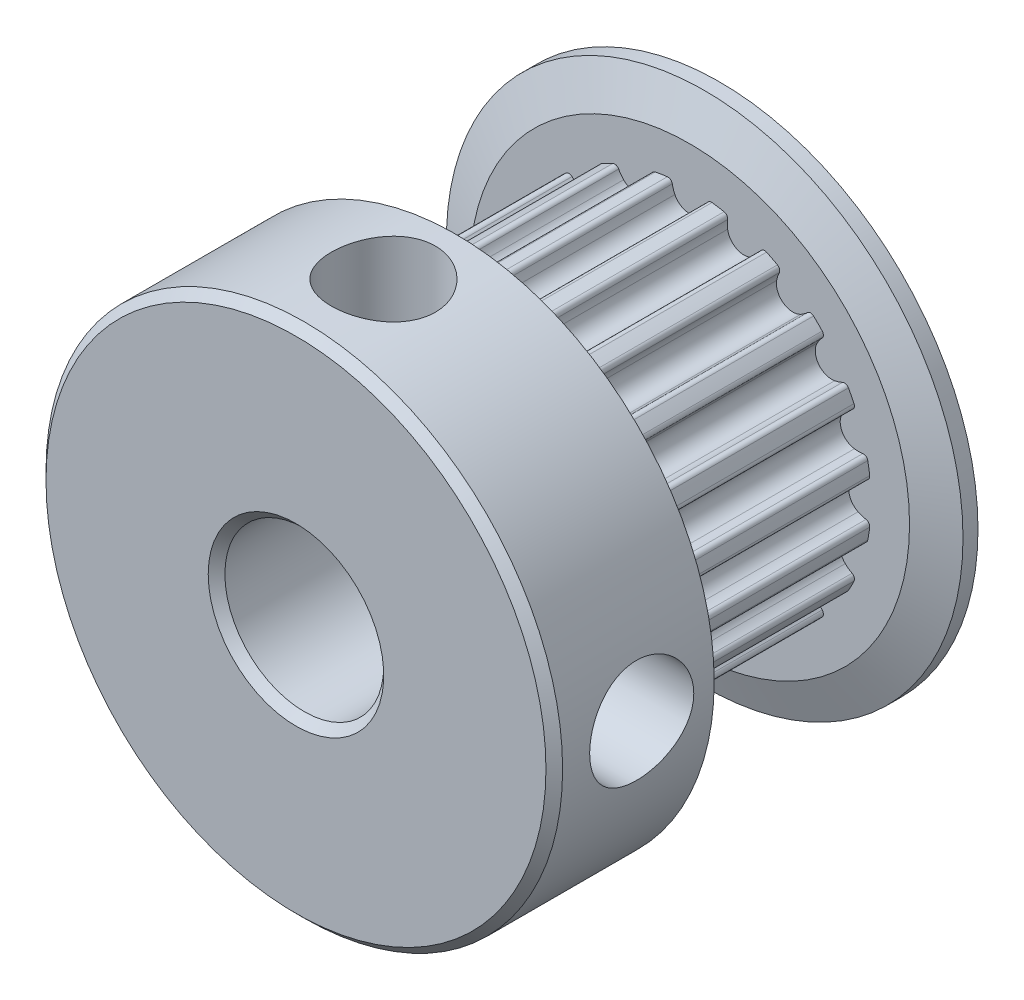
SolidWorks part; units mm, degrees
ref_plane "Front Plane" through (0, 0, 0) normal (0, 0, 1) x (1, 0, 0)
ref_plane "Top Plane" through (0, 0, 0) normal (0, 1, 0) x (1, 0, 0)
ref_plane "Right Plane" through (0, 0, 0) normal (1, 0, 0) x (0, 0, -1)
sketch "Sketch1" plane through (0, 0, 0) normal (0, 0, 1) x (1, 0, 0)
  line L1 (-1.7499, 5.3585) -> (1.7499, 5.3585) construction
  line L4 (0, 0) -> (0, 5.3585) construction
  line L5 (0, 5.3585) -> (0, 11.2119) construction
  line L6 (0, 6.3625) -> (1.9751, 6.0482) construction
  line L7 (1.9751, 6.0482) -> (2.6648, 5.8229) construction
  line L8 (1.9751, 6.0482) -> (1.7499, 5.3585) construction
  line L9 (-1.9751, 6.0482) -> (-1.7499, 5.3585) construction
  line L10 (-1.8963, 5.8067) -> (-2.841, 8.6995)
  line L11 (-2.841, 8.6995) -> (2.841, 8.6995)
  line L12 (2.841, 8.6995) -> (1.8963, 5.8067)
  circle A0 centre (0, 0) radius 6.3625 construction
  circle A1 centre (0, 0) radius 8.6995 construction
  circle A2 centre (0, 0) radius 6.1085 construction
  arc A3 (-0.4989, 5.6703) -> (0.4989, 5.6703) centre (0, 5.9135) ccw
  arc A4 (-0.4989, 5.6703) -> (-0.5855, 5.9387) centre (0.4, 6.1085) cw
  arc A5 (-1.8963, 5.8067) -> (-0.7518, 6.0621) centre (0, 0) cw
  arc A6 (-0.5855, 5.9387) -> (-0.7518, 6.0621) centre (-0.7333, 5.9132) ccw
  arc A7 (1.8963, 5.8067) -> (0.7518, 6.0621) centre (0, 0) ccw
  arc A8 (0.5855, 5.9387) -> (0.7518, 6.0621) centre (0.7333, 5.9132) cw
  arc A9 (0.4989, 5.6703) -> (0.5855, 5.9387) centre (-0.4, 6.1085) ccw
  point P6 (0, 20.9083)
  point P11 (0, 6.3625)
  point P13 (0, 8.6995)
  point P14 (0, 6.1085)
  dimension "D1" = 9.6964
  dimension "D2" = 4.8494
sketch "Sketch2" plane through (0, 0, 0) normal (1, 0, 0) x (0, 0, -1)
  line L0 (-7.135, 2.675) -> (7.135, 2.675)
  line L1 (-7.135, 2.675) -> (-7.135, 8.6995)
  line L2 (-1.75, 8.6995) -> (-7.135, 8.6995)
  line L3 (-2.255, 2.675) -> (-2.255, 8.6995) construction
  line L4 (-2.255, 8.6995) -> (-1.245, 8.6995) construction
  line L5 (-1.245, 8.6995) -> (-1.245, 6.1085) construction
  line L6 (-1.245, 6.1085) -> (6.125, 6.1085)
  line L7 (6.125, 6.1085) -> (6.125, 8.6995) construction
  line L8 (6.125, 8.6995) -> (7.135, 8.6995) construction
  line L9 (7.135, 8.6995) -> (7.135, 2.675)
  line L10 (-7.135, 0) -> (7.135, 0) construction
  line L11 (6.63, 8.6995) -> (6.125, 7.404)
  line L12 (-1.245, 7.404) -> (-1.75, 8.6995)
  line L14 (-1.245, 7.404) -> (-1.245, 6.1085)
  line L15 (6.125, 6.1085) -> (6.125, 7.404)
  line L16 (6.63, 8.6995) -> (7.135, 8.6995)
  arc A0 (-1.245, 7.404) -> (-1.75, 8.6995) centre (-3.1592, 7.404) ccw construction
  arc A1 (6.125, 7.404) -> (6.63, 8.6995) centre (8.0392, 7.404) cw construction
  point P12 (-1.245, 7.404)
  point P14 (-1.75, 8.6995)
  point P20 (6.125, 7.404)
  point P21 (6.63, 8.6995)
  point P25 (6.125, 0)
  point P26 (-1.245, 0)
  dimension "OA" = 14.27
  dimension "Bore" = 5.35
  dimension "Outside Width" = 8.38
  dimension "Inside Width" = 7.37
revolve "Revolve1" add sketch "Sketch2" angle 360 mid plane about L10
sketch "Sketch3" plane through (0, 0, 0) normal (0, 0, 1) x (1, 0, 0)
  line L6 (2.841, 8.6995) -> (-2.841, 8.6995)
  line L7 (1.8963, 5.8067) -> (2.841, 8.6995)
  line L8 (-2.841, 8.6995) -> (-1.8963, 5.8067)
  line L9 (2.841, 8.6995) -> (-2.841, 8.6995)
  line L10 (1.8963, 5.8067) -> (2.841, 8.6995)
  line L11 (-2.841, 8.6995) -> (-1.8963, 5.8067)
  arc A8 (1.8963, 5.8067) -> (0.7518, 6.0621) centre (0, 0) ccw
  arc A9 (0.7518, 6.0621) -> (0.5855, 5.9387) centre (0.7333, 5.9132) ccw
  arc A10 (0.4989, 5.6703) -> (0.5855, 5.9387) centre (-0.4, 6.1085) ccw
  arc A11 (-0.4989, 5.6703) -> (0.4989, 5.6703) centre (0, 5.9135) ccw
  arc A12 (-0.5855, 5.9387) -> (-0.4989, 5.6703) centre (0.4, 6.1085) ccw
  arc A13 (-0.5855, 5.9387) -> (-0.7518, 6.0621) centre (-0.7333, 5.9132) ccw
  arc A14 (-0.7518, 6.0621) -> (-1.8963, 5.8067) centre (0, 0) ccw
  arc A15 (1.8963, 5.8067) -> (0.7518, 6.0621) centre (0, 0) ccw
  arc A16 (0.7518, 6.0621) -> (0.5855, 5.9387) centre (0.7333, 5.9132) ccw
  arc A17 (0.4989, 5.6703) -> (0.5855, 5.9387) centre (-0.4, 6.1085) ccw
  arc A18 (-0.4989, 5.6703) -> (0.4989, 5.6703) centre (0, 5.9135) ccw
  arc A19 (-0.5855, 5.9387) -> (-0.4989, 5.6703) centre (0.4, 6.1085) ccw
  arc A20 (-0.5855, 5.9387) -> (-0.7518, 6.0621) centre (-0.7333, 5.9132) ccw
  arc A21 (-0.7518, 6.0621) -> (-1.8963, 5.8067) centre (0, 0) ccw
  dimension "D1" = 0
extrude "Cut-Extrude1" cut sketch "Sketch3" against normal up to vertex (6.125 mm away) from vertex up to point (0, 6.1085, -6.125) starting at point (0, 6.1085, 1.245)
pattern_circular "CirPattern1" count 20 over 360 about axis through (0, 0, 7.135) along (0, 0, 1) of "Cut-Extrude1"
sketch "Sketch4" plane through (0, 0, 0) normal (1, 0, 0) x (0, -1, 0)
  line L0 (0, -1.245) -> (0, -7.135) construction
  line L1 (-2.675, -7.135) -> (2.675, -7.135) construction
  line L2 (7.404, -1.245) -> (-7.404, -1.245) construction
  circle A0 centre (0, -4.19) radius 1.7526
extrude "Cut-Extrude2" cut sketch "Sketch4" along normal through all
ref_plane "Plane1" through (0, 0, 4.19) normal (0, 0, 1) x (1, 0, 0)
sketch "Sketch5" plane through (0, 0, 4.19) normal (0, 0, 1) x (1, 0, 0)
  line L0 (0, 0) -> (0, 8.6995) construction
  line L1 (2.675, -1.3716) -> (2.675, 0)
  line L2 (3.056, -1.7526) -> (8.1401, -1.7526)
  line L3 (2.675, 0) -> (8.6995, 0) construction
  line L4 (2.675, 0) -> (8.5211, 0)
  line L5 (8.5211, 0) -> (8.5211, -1.3716)
  line L6 (3.056, -1.7526) -> (2.675, -1.3716)
  line L7 (8.5211, -1.3716) -> (8.1401, -1.7526)
  circle A0 centre (0, 0) radius 8.6995 construction
  circle A1 centre (0, 0) radius 2.675 construction
  point P2 (2.675, -1.7526)
  point P11 (8.5211, -1.7526)
revolve "Revolve2" [suppressed] add sketch "Sketch5" angle 360 mid plane about L4
sketch "Sketch6" [suppressed] plane through (8.5211, 5.3841, 0) normal (-1, 0, 0) x (0, -1, 0)
  line L1 (5.3841, 5.2019) -> (4.5078, 4.6959)
  line L2 (4.5078, 4.6959) -> (4.5078, 3.6841)
  line L3 (4.5078, 3.6841) -> (5.3841, 3.1781)
  line L4 (5.3841, 3.1781) -> (6.2604, 3.6841)
  line L5 (6.2604, 3.6841) -> (6.2604, 4.6959)
  line L6 (6.2604, 4.6959) -> (5.3841, 5.2019)
  circle A0 centre (5.3841, 4.19) radius 0.8763 construction
  dimension "D1" = 1.7526
extrude "Cut-Extrude3" [suppressed] cut sketch "Sketch6" along normal blind 1.3144
pattern_circular "CirPattern3" count 2 over 90 about axis through (0, 0, 7.135) along (0, 0, 1) of "Cut-Extrude2", "Revolve2", "Cut-Extrude3"
chamfer "Chamfer1" distance 0.2807 angle 45 2 edges at (2.675, 0, 7.135) (8.6995, 0, 7.135)
ref_axis "Center Axis 1" through (0, 0, -7.135) along (0, 0, 1)
ref_plane "Contact Plane 1" through (0, 0, 7.135) normal (0, 0, 1) x (1, 0, 0)
ref_plane "Contact Plane 2" through (0, 0, -7.135) normal (0, 0, -1) x (-1, 0, 0)
equation "\"D2@Sketch1\"= \"D1@Sketch1\" / 2"
equation "\"D1@Sketch6\" = \"Set Screw@Sketch4\" / 2"
equation "\"D1@Cut-Extrude3\" = \"D1@Sketch6\"*.75"
